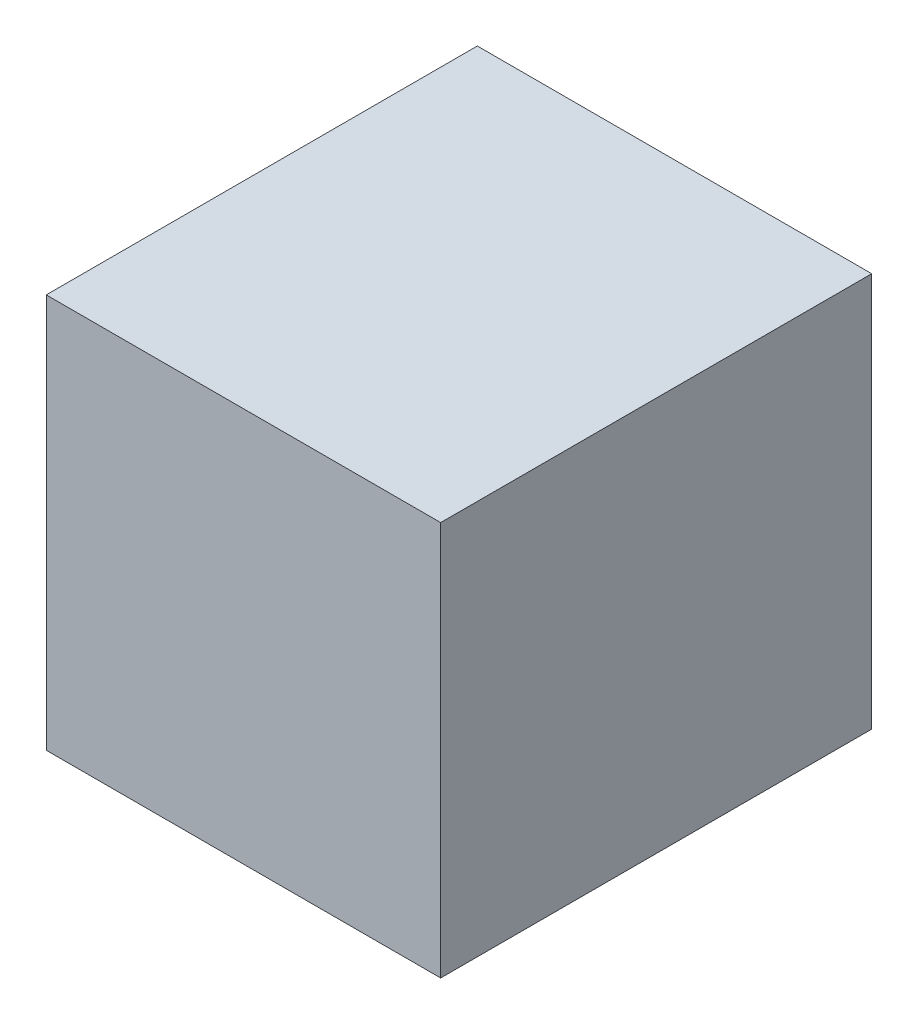
SolidWorks part; units mm, degrees
ref_plane "前视基准面" through (0, 0, 0) normal (0, 0, 1) x (1, 0, 0)
ref_plane "上视基准面" through (0, 0, 0) normal (0, 1, 0) x (1, 0, 0)
ref_plane "右视基准面" through (0, 0, 0) normal (1, 0, 0) x (0, 0, -1)
sketch "草图1" plane through (0, 0, 0) normal (0, 0, 1) x (1, 0, 0)
  line L1 (0, 0) -> (100, 0)
  line L2 (0, 0) -> (0, 100)
  line L3 (0, 100) -> (100, 100)
  line L4 (100, 0) -> (100, 100)
  dimension "D1" = 100
ref_plane "基准面1" through (0, 0, 86.6) normal (0, 0, 1) x (1, 0, 0)
sketch "草图2" plane through (0, 0, 86.6) normal (0, 0, 1) x (1, 0, 0)
  line L0 (-22.6947, 77.3053) -> (0, 100) construction
  line L1 (-22.6947, -22.6947) -> (77.3053, -22.6947)
  line L2 (-22.6947, -22.6947) -> (-22.6947, 77.3053)
  line L3 (-22.6947, 77.3053) -> (77.3053, 77.3053)
  line L4 (77.3053, -22.6947) -> (77.3053, 77.3053)
  line L5 (0, 100) -> (100, 100) construction
  line L6 (100, 0) -> (100, 100) construction
  dimension "D1" = 135
loft "放样1" add profiles "草图1", "草图2" connector at (0, 0, 0) connector at (-22.6947, -22.6947, 86.6)
